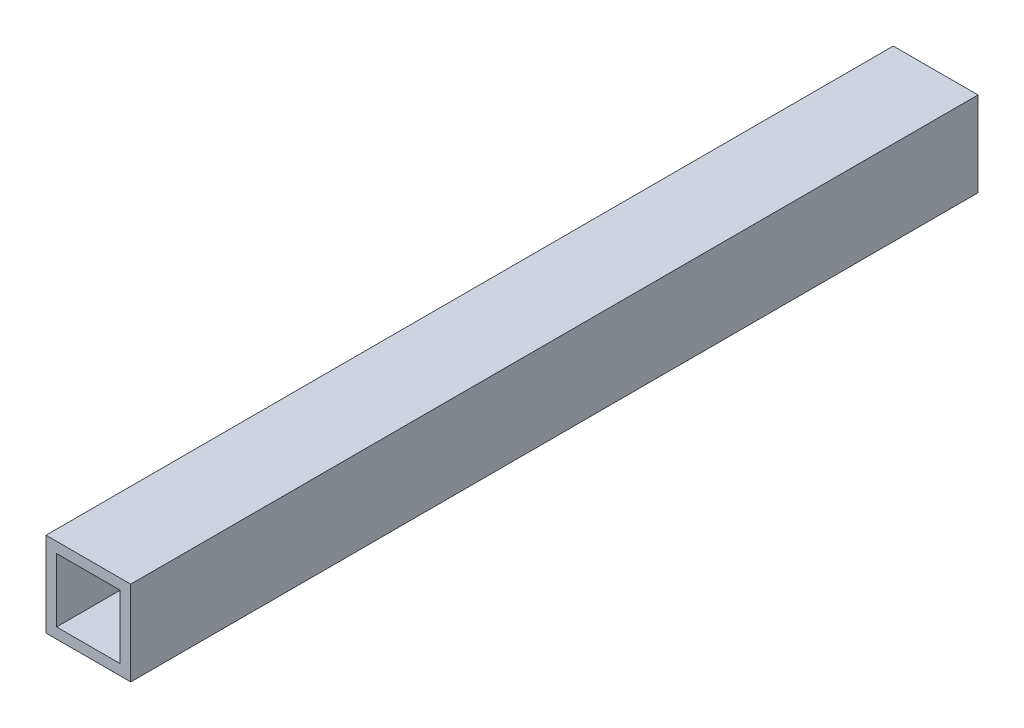
SolidWorks part; units mm, degrees
ref_plane "Front Plane" through (0, 0, 0) normal (0, 0, 1) x (1, 0, 0)
ref_plane "Top Plane" through (0, 0, 0) normal (0, 1, 0) x (1, 0, 0)
ref_plane "Right Plane" through (0, 0, 0) normal (1, 0, 0) x (0, 0, -1)
sketch "Sketch1" plane through (0, 0, 0) normal (0, 0, 1) x (1, 0, 0)
  line L1 (-12.7, -12.7) -> (12.7, -12.7)
  line L2 (-12.7, -12.7) -> (-12.7, 12.7)
  line L3 (-12.7, 12.7) -> (12.7, 12.7)
  line L4 (12.7, -12.7) -> (12.7, 12.7)
  line L5 (-12.7, -12.7) -> (12.7, 12.7) construction
  line L6 (-12.7, 12.7) -> (12.7, -12.7) construction
  point P0 (0, 0)
  dimension "D1" = 25.4
  dimension "D2" = 25.4
extrude "Boss-Extrude1" add sketch "Sketch1" along normal mid plane 254
shell "Shell1" thickness 3.175 removed face at (0, 0, -127) removed face at (0, 0, 127)
